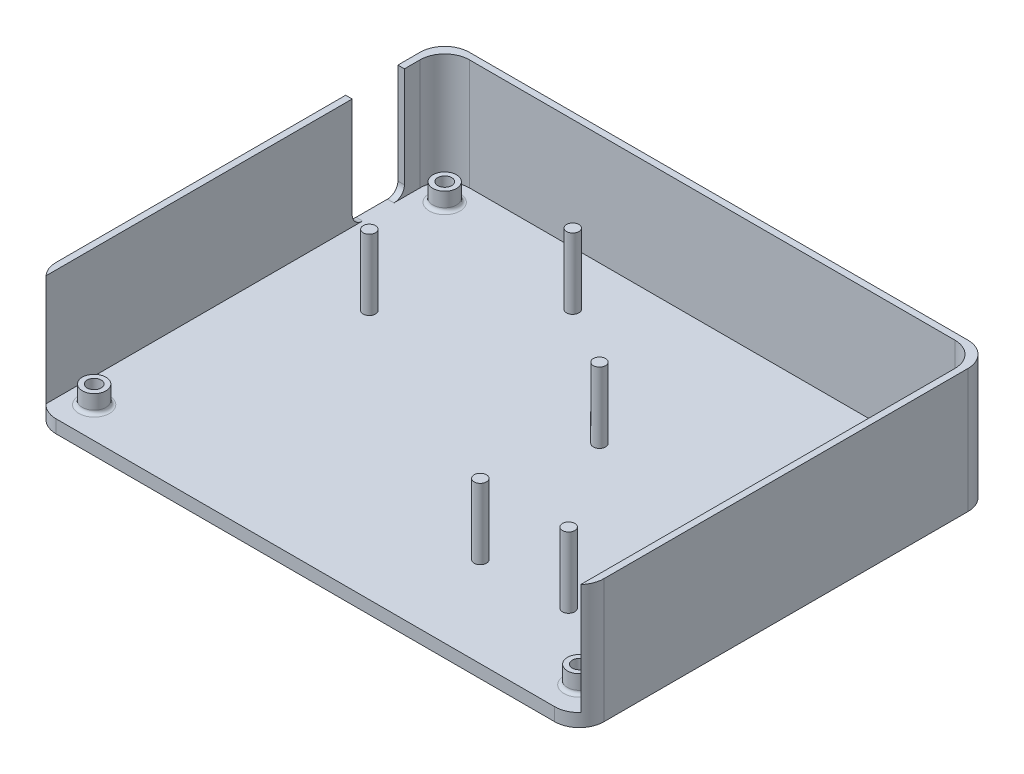
SolidWorks part; units mm, degrees
ref_plane "Front Plane" through (0, 0, 0) normal (0, 0, 1) x (1, 0, 0)
ref_plane "Top Plane" through (0, 0, 0) normal (0, 1, 0) x (1, 0, 0)
ref_plane "Right Plane" through (0, 0, 0) normal (1, 0, 0) x (0, 0, -1)
sketch "Sketch1" plane through (0, 0, 0) normal (0, 1, 0) x (1, 0, 0)
  line L0 (-66.8583, -50.2762) -> (-65.2708, -50.2762)
  line L1 (-65.2708, -50.2762) -> (64.8554, -50.2762)
  line L2 (-66.8583, -50.2762) -> (-66.8583, 44.2663)
  line L3 (-60.8583, 50.2663) -> (60.4429, 50.2663)
  line L4 (66.4429, -50.2762) -> (66.4429, 44.2663)
  line L5 (66.4429, -50.2762) -> (64.8554, -50.2762)
  line L6 (-50.3864, 41.1329) -> (-50.3864, 5.0649)
  line L7 (-50.3483, 41.1463) -> (49.9329, 41.1463)
  line L8 (-65.2708, -50.2762) -> (-65.2708, 42.6788)
  line L9 (-59.2708, 48.6788) -> (58.8554, 48.6788)
  line L10 (64.8554, -50.2762) -> (64.8554, 42.6788)
  line L11 (-50.3483, 41.1463) -> (-50.3483, -40.1162)
  line L12 (-50.3483, -40.1162) -> (49.9329, -40.1162)
  line L13 (49.9329, 41.1463) -> (49.9329, -40.1162)
  line L14 (-50.3864, 5.0649) -> (14.3836, 5.0649)
  line L15 (14.3836, 5.0649) -> (14.3836, -33.7971)
  line L16 (14.3836, -33.7971) -> (47.4036, -33.7971)
  line L17 (47.4036, -33.7971) -> (47.4036, 41.1329)
  line L18 (47.4036, 41.1329) -> (-50.3864, 41.1329)
  circle A0 centre (-59.2383, 42.6463) radius 1.7
  circle A1 centre (-59.2383, 42.6463) radius 2.875
  circle A2 centre (58.8229, 42.6463) radius 2.875
  circle A3 centre (58.8229, 42.6463) radius 1.7
  circle A4 centre (-59.2383, -42.6562) radius 2.875
  circle A5 centre (-59.2383, -42.6562) radius 1.7
  circle A6 centre (58.8229, -42.6562) radius 2.875
  circle A7 centre (58.8229, -42.6562) radius 1.7
  circle A8 centre (-21.0872, 35.6529) radius 1.5
  circle A9 centre (20.4128, -28.3471) radius 1.5
  circle A10 centre (-45.5872, 10.6529) radius 1.5
  circle A11 centre (10.4128, 10.6529) radius 1.5
  circle A12 centre (41.4128, -27.8471) radius 1.5
  arc A13 (-66.8583, 44.2663) -> (-60.8583, 50.2663) centre (-60.8583, 44.2663) cw
  arc A14 (-65.2708, 42.6788) -> (-59.2708, 48.6788) centre (-59.2708, 42.6788) cw
  circle A15 centre (-48.0512, -37.8237) radius 2
  arc A16 (58.8554, 48.6788) -> (64.8554, 42.6788) centre (58.8554, 42.6788) cw
  arc A17 (60.4429, 50.2663) -> (66.4429, 44.2663) centre (60.4429, 44.2663) cw
  point P0 (0, 0)
  point P44 (-66.8583, 50.2663)
  point P53 (66.4429, 50.2663)
  dimension "D5" = 7.62
  dimension "D7" = 7.62
  dimension "D18" = 97.79
  dimension "D20" = 64.77
  dimension "D26" = 24.5
  dimension "D32" = 6
  dimension "D33" = 6
  dimension "D34" = 6
  dimension "D1" = 133.3013
  dimension "D2" = 100.5425
  dimension "D3" = 1.5875
  dimension "D4" = 1.5875
  dimension "D6" = 7.62
  dimension "D8" = 7.62
  dimension "D9" = 7.62
  dimension "D10" = 7.62
  dimension "D11" = 7.62
  dimension "D12" = 7.62
  dimension "D13" = 1.5875
  dimension "D14" = 9.12
  dimension "D15" = 16.51
  dimension "D16" = 16.51
  dimension "D17" = 81.2625
  dimension "D19" = 36.068
  dimension "D21" = 74.93
  dimension "D22" = 5.588
  dimension "D23" = 5.588
  dimension "D24" = 7.366
  dimension "D25" = 56
  dimension "D27" = 25
  dimension "D28" = 10
  dimension "D29" = 21
  dimension "D30" = 39
  dimension "D31" = 0.5
extrude "Boss-Extrude12" add sketch "Sketch1" along normal blind 3.175 contours L5 L4 A17 L3 A13 L2 L0 L1
extrude "Boss-Extrude13" add sketch "Sketch1<23>" along normal blind 30.1625 contours L10 L5 L4 L3 L2 L0 L8 L9 region at (-66.6913, 0, 3.005)
sketch "Sketch1<23>" plane through (0, 0, 0) normal (0, 1, 0) x (1, 0, 0) same geometry as "Sketch1"
extrude "Boss-Extrude15" add sketch "Sketch1<25>" along normal blind 7.525 contours A1 A0 | A2 A3 | A6 A7 | A4 A5 region at (-62.032, 0, -42.6463) region at (56.0293, 0, -42.6463) region at (-62.032, 0, 42.6562) region at (56.0293, 0, 42.6562)
sketch "Sketch1<25>" plane through (0, 0, 0) normal (0, 1, 0) x (1, 0, 0) same geometry as "Sketch1"
extrude "Cut-Extrude3" cut sketch "Sketch1<27>" along normal blind 28.575 contours A5 | A5 | A0 | A3 | A7 region at (-59.2383, 0, 42.6562)
sketch "Sketch1<27>" plane through (0, 0, 0) normal (0, 1, 0) x (1, 0, 0) same geometry as "Sketch1"
chamfer "Chamfer2" distance 1.45 angle 45 4 edges at (58.8229, 0, 44.3562) (58.8229, 0, -40.9463) (-59.2383, 0, 44.3562) (-59.2383, 0, -40.9463)
extrude "Boss-Extrude16" add sketch "Sketch1<28>" along normal blind 20.32 contours A12 | A9 | A8 | A10 | A11 region at (20.4128, 0, 28.3471) region at (41.4128, 0, 27.8471)
sketch "Sketch1<28>" plane through (0, 0, 0) normal (0, 1, 0) x (1, 0, 0) same geometry as "Sketch1"
fillet "Fillet3" radius 6 2 edges at (66.4429, 15.0812, 50.2762) (-66.8583, 15.0812, 50.2762)
fillet "Fillet4" radius 0.85 1 edges at (-59.2383, 3.175, -45.5213)
fillet "Fillet5" radius 0.85 3 edges at (-59.2383, 3.175, 39.7812) (58.8229, 3.175, 39.7812) (58.8229, 3.175, -45.5213)
sketch "Sketch2" plane through (-65.2708, 0, 0) normal (1, 0, 0) x (0, 0, -1)
  line L0 (-48.3419, 3.175) -> (42.6788, 3.175) construction
  line L1 (38.8698, 3.175) -> (26.1698, 3.175)
  line L2 (38.8698, 3.175) -> (38.8698, 30.1625)
  line L3 (38.8698, 30.1625) -> (26.1698, 30.1625)
  line L4 (26.1698, 3.175) -> (26.1698, 30.1625)
  line L5 (-48.3419, 30.1625) -> (42.6788, 30.1625) construction
  line L6 (42.6788, 30.1625) -> (42.6788, 3.175) construction
  dimension "D1" = 12.7
  dimension "D2" = 3.8089
extrude "Cut-Extrude4" cut sketch "Sketch2" against normal blind 2.54
fillet "Fillet6" radius 2.54 2 edges at (-66.0646, 3.175, -38.8698) (-66.0646, 3.175, -26.1698)
